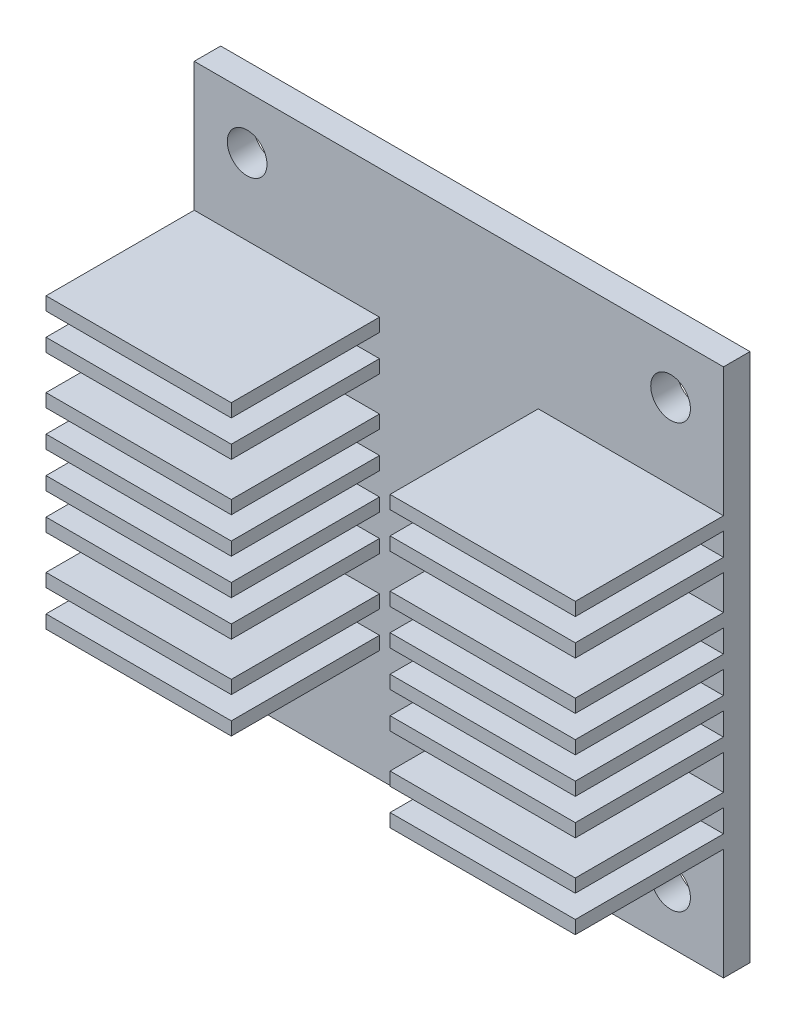
SolidWorks part; units mm, degrees
ref_plane "Front Plane" through (0, 0, 0) normal (0, 0, 1) x (1, 0, 0)
ref_plane "Top Plane" through (0, 0, 0) normal (0, 1, 0) x (1, 0, 0)
ref_plane "Right Plane" through (0, 0, 0) normal (1, 0, 0) x (0, 0, -1)
sketch "Sketch1" plane through (0, 0, 0) normal (0, 0, 1) x (1, 0, 0)
  line L0 (41, 4.4837) -> (27, 4.4837)
  line L1 (41, 2.4837) -> (1, 2.4837)
  line L2 (41, 2.4837) -> (41, 42.4837)
  line L3 (41, 42.4837) -> (1, 42.4837)
  line L4 (1, 2.4837) -> (1, 42.4837)
  line L5 (21, 40.4837) -> (21, 4.4837) construction
  line L6 (41, 21.7785) -> (27, 21.7785) construction
  line L7 (41, 4.4837) -> (41, 40.4837)
  line L8 (27, 4.4837) -> (27, 40.4837)
  line L9 (15, 4.4837) -> (15, 40.4837)
  line L10 (1, 4.4837) -> (1, 40.4837)
  line L11 (25, 4.4837) -> (25, 40.4837)
  line L12 (17, 4.4837) -> (17, 40.4837)
  line L13 (41, 40.4837) -> (27, 40.4837)
  line L14 (41, 5.4837) -> (27, 5.4837)
  line L15 (41, 6.389) -> (27, 6.389)
  line L16 (41, 7.2943) -> (27, 7.2943)
  line L17 (41, 8.1995) -> (27, 8.1995)
  line L18 (41, 9.1048) -> (27, 9.1048)
  line L19 (41, 10.01) -> (27, 10.01)
  line L20 (41, 10.9153) -> (27, 10.9153)
  line L21 (41, 11.8206) -> (27, 11.8206)
  line L22 (41, 12.7258) -> (27, 12.7258)
  line L23 (41, 13.6311) -> (27, 13.6311)
  line L24 (41, 14.5364) -> (27, 14.5364)
  line L25 (41, 15.4416) -> (27, 15.4416)
  line L26 (41, 16.3469) -> (27, 16.3469)
  line L27 (41, 17.2522) -> (27, 17.2522)
  line L28 (41, 18.1574) -> (27, 18.1574)
  line L29 (41, 19.0627) -> (27, 19.0627)
  line L30 (41, 19.9679) -> (27, 19.9679)
  line L31 (41, 20.8732) -> (27, 20.8732)
  line L32 (41, 21.7785) -> (27, 21.7785)
  line L33 (41, 22.6837) -> (27, 22.6837)
  line L34 (41, 23.589) -> (27, 23.589)
  line L35 (41, 24.4943) -> (27, 24.4943)
  line L36 (41, 25.3995) -> (27, 25.3995)
  line L37 (41, 26.3048) -> (27, 26.3048)
  line L38 (41, 27.21) -> (27, 27.21)
  line L39 (41, 28.1153) -> (27, 28.1153)
  line L40 (41, 29.0206) -> (27, 29.0206)
  line L41 (41, 29.9258) -> (27, 29.9258)
  line L42 (41, 30.8311) -> (27, 30.8311)
  line L43 (41, 31.7364) -> (27, 31.7364)
  line L44 (41, 32.6416) -> (27, 32.6416)
  line L45 (41, 33.5469) -> (27, 33.5469)
  line L46 (41, 34.4522) -> (27, 34.4522)
  line L47 (41, 35.3574) -> (27, 35.3574)
  line L48 (41, 36.2627) -> (27, 36.2627)
  line L49 (41, 37.1679) -> (27, 37.1679)
  line L50 (41, 38.0732) -> (27, 38.0732)
  line L51 (46.6374, 3.6837) -> (46.6374, 4.6837) construction
  line L52 (45.6374, 5.4837) -> (-11.288, 5.4837) construction
  line L53 (45.6374, 4.4837) -> (-11.288, 4.4837) construction
  line L54 (25, 4.4837) -> (17, 4.4837)
  line L55 (25, 5.4837) -> (17, 5.4837)
  line L56 (25, 6.389) -> (17, 6.389)
  line L57 (25, 7.2943) -> (17, 7.2943)
  line L58 (25, 8.1995) -> (17, 8.1995)
  line L59 (25, 9.1048) -> (17, 9.1048)
  line L60 (25, 10.01) -> (17, 10.01)
  line L61 (25, 10.9153) -> (17, 10.9153)
  line L62 (25, 11.8206) -> (17, 11.8206)
  line L63 (25, 12.7258) -> (17, 12.7258)
  line L64 (25, 13.6311) -> (17, 13.6311)
  line L65 (25, 14.5364) -> (17, 14.5364)
  line L66 (25, 15.4416) -> (17, 15.4416)
  line L67 (25, 16.3469) -> (17, 16.3469)
  line L68 (25, 17.2522) -> (17, 17.2522)
  line L69 (25, 18.1574) -> (17, 18.1574)
  line L70 (25, 19.0627) -> (17, 19.0627)
  line L71 (25, 19.9679) -> (17, 19.9679)
  line L72 (25, 20.8732) -> (17, 20.8732)
  line L73 (25, 21.7785) -> (17, 21.7785) construction
  line L74 (25, 21.7785) -> (17, 21.7785)
  line L75 (25, 22.6837) -> (17, 22.6837)
  line L76 (25, 23.589) -> (17, 23.589)
  line L77 (25, 24.4943) -> (17, 24.4943)
  line L78 (25, 25.3995) -> (17, 25.3995)
  line L79 (25, 26.3048) -> (17, 26.3048)
  line L80 (25, 27.21) -> (17, 27.21)
  line L81 (25, 28.1153) -> (17, 28.1153)
  line L82 (25, 29.0206) -> (17, 29.0206)
  line L83 (25, 29.9258) -> (17, 29.9258)
  line L84 (25, 30.8311) -> (17, 30.8311)
  line L85 (25, 31.7364) -> (17, 31.7364)
  line L86 (25, 32.6416) -> (17, 32.6416)
  line L87 (25, 33.5469) -> (17, 33.5469)
  line L88 (25, 34.4522) -> (17, 34.4522)
  line L89 (25, 35.3574) -> (17, 35.3574)
  line L90 (25, 36.2627) -> (17, 36.2627)
  line L91 (25, 37.1679) -> (17, 37.1679)
  line L92 (25, 38.0732) -> (17, 38.0732)
  line L93 (25, 40.4837) -> (17, 40.4837)
  line L94 (15, 4.4837) -> (1, 4.4837)
  line L95 (15, 5.4837) -> (1, 5.4837)
  line L96 (15, 6.389) -> (1, 6.389)
  line L97 (15, 7.2943) -> (1, 7.2943)
  line L98 (15, 8.1995) -> (1, 8.1995)
  line L99 (15, 9.1048) -> (1, 9.1048)
  line L100 (15, 10.01) -> (1, 10.01)
  line L101 (15, 10.9153) -> (1, 10.9153)
  line L102 (15, 11.8206) -> (1, 11.8206)
  line L103 (15, 12.7258) -> (1, 12.7258)
  line L104 (15, 13.6311) -> (1, 13.6311)
  line L105 (15, 14.5364) -> (1, 14.5364)
  line L106 (15, 15.4416) -> (1, 15.4416)
  line L107 (15, 16.3469) -> (1, 16.3469)
  line L108 (15, 17.2522) -> (1, 17.2522)
  line L109 (15, 18.1574) -> (1, 18.1574)
  line L110 (15, 19.0627) -> (1, 19.0627)
  line L111 (15, 19.9679) -> (1, 19.9679)
  line L112 (15, 20.8732) -> (1, 20.8732)
  line L113 (15, 21.7785) -> (1, 21.7785) construction
  line L114 (15, 21.7785) -> (1, 21.7785)
  line L115 (15, 22.6837) -> (1, 22.6837)
  line L116 (15, 23.589) -> (1, 23.589)
  line L117 (15, 24.4943) -> (1, 24.4943)
  line L118 (15, 25.3995) -> (1, 25.3995)
  line L119 (15, 26.3048) -> (1, 26.3048)
  line L120 (15, 27.21) -> (1, 27.21)
  line L121 (15, 28.1153) -> (1, 28.1153)
  line L122 (15, 29.0206) -> (1, 29.0206)
  line L123 (15, 29.9258) -> (1, 29.9258)
  line L124 (15, 30.8311) -> (1, 30.8311)
  line L125 (15, 31.7364) -> (1, 31.7364)
  line L126 (15, 32.6416) -> (1, 32.6416)
  line L127 (15, 33.5469) -> (1, 33.5469)
  line L128 (15, 34.4522) -> (1, 34.4522)
  line L129 (15, 35.3574) -> (1, 35.3574)
  line L130 (15, 36.2627) -> (1, 36.2627)
  line L131 (15, 37.1679) -> (1, 37.1679)
  line L132 (15, 38.0732) -> (1, 38.0732)
  line L133 (15, 40.4837) -> (1, 40.4837)
  point P48 (21, 21.7785)
  dimension "D1" = 2
  dimension "D2" = 2
  dimension "D3" = 0
  dimension "D4" = 0
  dimension "D5" = 2
  dimension "D6" = 2
  dimension "D7" = 14
  dimension "D8" = 14
  dimension "D10" = 1
  dimension "D9" = 1
extrude "Boss-Extrude1" add sketch "Sketch1" along normal blind 2 contours L1 L4 L3 L2
extrude "Extrude-Thin1" add sketch "Sketch1<3>" along normal blind 11.2 from surface thin contours L20 | L101 | L23 | L104 | L36 | L33 | L30 | L27 | L108 | L111 | L115 | L118 | L40 | L122 | L43 | L125 starting at face at (21, 22.4837, 2) thin type one direction wall 1
sketch "Sketch1<3>" plane through (0, 0, 0) normal (0, 0, 1) x (1, 0, 0) same geometry as "Sketch1"
sketch "Sketch3" plane through (0, 0, 0) normal (0, 0, -1) x (-1, 0, 0)
  line L1 (-21, 2.4837) -> (-21, 42.4837) construction
  line L2 (-5, 38.4837) -> (-37, 38.4837) construction
  line L3 (-5, 38.4837) -> (-5, 6.4837) construction
  line L4 (-5, 6.4837) -> (-37, 6.4837) construction
  line L5 (-37, 38.4837) -> (-37, 6.4837) construction
  line L6 (-21, 6.4837) -> (-21, 38.4837) construction
  line L7 (-5, 22.4837) -> (-37, 22.4837) construction
  line L8 (-41, 2.4837) -> (-1, 2.4837) construction
  line L9 (-41, 42.4837) -> (-1, 42.4837) construction
  line L10 (-41, 22.4837) -> (-1, 22.4837) construction
  line L11 (-41, 2.4837) -> (-41, 42.4837) construction
  line L12 (-1, 2.4837) -> (-1, 42.4837) construction
  circle A0 centre (-37, 6.4837) radius 1.5
  circle A1 centre (-5, 6.4837) radius 1.5
  circle A2 centre (-5, 38.4837) radius 1.5
  circle A3 centre (-37, 38.4837) radius 1.5
  point P141 (-21, 22.4837)
  dimension "D1" = 3
  dimension "D4" = 3
  dimension "D5" = 3
  dimension "D6" = 3
  dimension "D2" = 32
  dimension "D3" = 32
extrude "Cut-Extrude1" cut sketch "Sketch3" along direction (0, 0, 1) on the side against the normal up to vertex (2 mm away) from vertex contours A0 up to point (1, 2.4837, 2) starting at point (1, 2.4837, 0)
pattern_linear "LPattern1" count 2 spacing 32 along (-1, 0, 0) count 2 spacing 32 along (0, 1, 0) of "Cut-Extrude1"
